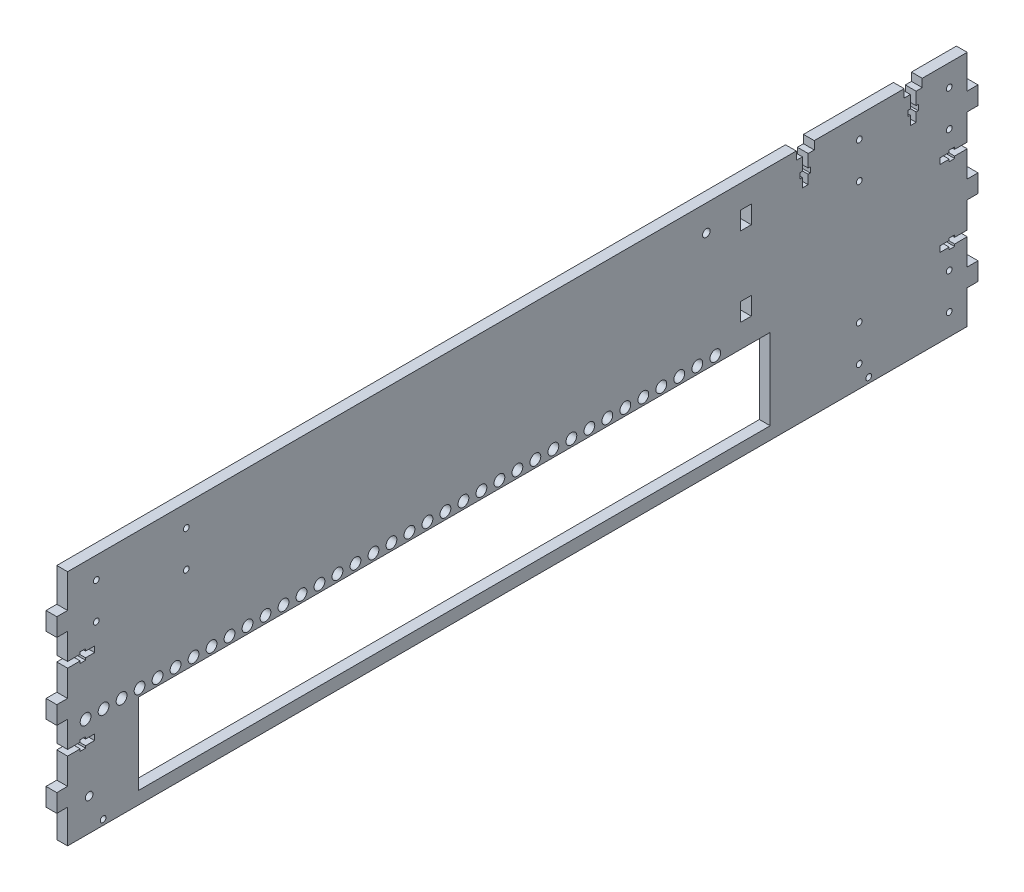
SolidWorks part; units mm, degrees
ref_plane "Front Plane" through (0, 0, 0) normal (0, 0, 1) x (1, 0, 0)
ref_plane "Top Plane" through (0, 0, 0) normal (0, 1, 0) x (1, 0, 0)
ref_plane "Right Plane" through (0, 0, 0) normal (1, 0, 0) x (0, 0, -1)
sketch "Sketch1" plane through (0, 0, 0) normal (1, 0, 0) x (0, 0, -1)
  line L1 (-250, -66) -> (250, -66)
  line L2 (-250, -66) -> (-250, 66)
  line L3 (-250, 66) -> (250, 66)
  line L4 (250, -66) -> (250, 66)
  line L5 (-250, -66) -> (250, 66) construction
  line L6 (-250, 66) -> (250, -66) construction
  point P0 (0, 0)
  dimension "D1" = 132
  dimension "D2" = 500
extrude "Boss-Extrude1" add sketch "Sketch1" along normal blind 6
sketch "Sketch4" plane through (0, 0, 250) normal (0, 0, 1) x (1, 0, 0)
  line L0 (0, 66) -> (0, -66) construction
  line L1 (0, 47.3321) -> (6, 47.3321)
  line L2 (0, 47.3321) -> (0, 37.3321)
  line L3 (0, 37.3321) -> (6, 37.3321)
  line L4 (6, 47.3321) -> (6, 37.3321)
  line L5 (6, 66) -> (6, -66) construction
  line L6 (0, 37.3321) -> (6, 37.3321) construction
  line L7 (0, -66) -> (0, 66) construction
  line L8 (6, 47.3321) -> (0, 47.3321) construction
  line L9 (0, -5) -> (6, -5) construction
  line L10 (0, -5) -> (6, -5)
  line L11 (0, -5) -> (0, 5)
  line L12 (0, 5) -> (6, 5)
  line L13 (6, -5) -> (6, 5)
  line L14 (6, -66) -> (6, 66) construction
  line L15 (6, 5) -> (0, 5) construction
  line L16 (6, -37.3321) -> (0, -37.3321) construction
  line L17 (0, -47.3321) -> (6, -47.3321)
  line L18 (0, -47.3321) -> (0, -37.3321)
  line L19 (0, -37.3321) -> (6, -37.3321)
  line L20 (6, -47.3321) -> (6, -37.3321)
  line L21 (0, -47.3321) -> (6, -47.3321) construction
extrude "Boss-Extrude2" add sketch "Sketch4" along normal blind 6
sketch "Sketch5" plane through (0, 0, 0) normal (-1, 0, 0) x (0, 0, 1)
  line L1 (250, 22.7661) -> (250, 19.5661) construction
  line L3 (250, 22.7661) -> (250, 19.5661) construction
  line L4 (250, -19.5661) -> (250, -22.7661) construction
  line L5 (250, -19.5661) -> (250, -22.7661) construction
  line L6 (250, 21.1661) -> (235, 21.1661) construction
  line L7 (250, -21.1661) -> (235, -21.1661) construction
  line L8 (250, -19.5661) -> (243, -19.5661)
  line L9 (250, 22.7661) -> (243, 22.7661)
  line L10 (250, -22.7661) -> (243, -22.7661)
  line L11 (250, 19.5661) -> (243, 19.5661)
  line L12 (250, -19.5661) -> (250, -22.7661)
  line L13 (235, -19.5661) -> (235, -22.7661)
  line L14 (250, 22.7661) -> (250, 19.5661)
  line L15 (235, 22.7661) -> (235, 19.5661)
  line L16 (240, 19.5661) -> (235, 19.5661)
  line L17 (243, 18.3661) -> (240, 18.3661)
  line L18 (243, 18.3661) -> (243, 19.5661)
  line L19 (243, 23.9661) -> (240, 23.9661)
  line L20 (240, 18.3661) -> (240, 19.5661)
  line L21 (243, 18.3661) -> (240, 23.9661) construction
  line L22 (243, 23.9661) -> (240, 18.3661) construction
  line L23 (243, -23.9661) -> (240, -23.9661)
  line L24 (243, -23.9661) -> (243, -22.7661)
  line L25 (243, -18.3661) -> (240, -18.3661)
  line L26 (240, -23.9661) -> (240, -22.7661)
  line L27 (243, -23.9661) -> (240, -18.3661) construction
  line L28 (243, -18.3661) -> (240, -23.9661) construction
  line L29 (250, 19.5661) -> (235, 19.5661) construction
  line L30 (243, 22.7661) -> (243, 23.9661)
  line L31 (240, 22.7661) -> (235, 22.7661)
  line L32 (250, 22.7661) -> (235, 22.7661) construction
  line L33 (240, 22.7661) -> (240, 23.9661)
  line L34 (240, -19.5661) -> (235, -19.5661)
  line L35 (250, -19.5661) -> (235, -19.5661) construction
  line L36 (240, -19.5661) -> (240, -18.3661)
  line L37 (240, -22.7661) -> (235, -22.7661)
  line L38 (250, -22.7661) -> (235, -22.7661) construction
  line L39 (243, -19.5661) -> (243, -18.3661)
  point P20 (241.5, 21.1661)
  point P25 (241.5, -21.1661)
  line M35 (250, -37.3321) -> (250, -5)
  line M39 (250, 5) -> (250, 37.3321)
  dimension "D3" = 1.6
  dimension "D4" = 7
  dimension "D5" = 3
  dimension "D6" = 5.6
  dimension "D1" = 15
  dimension "D7" = 7
  dimension "D8" = 3
  dimension "D9" = 5.6
  dimension "D2" = 1.6
extrude "Cut-Extrude3" cut sketch "Sketch5" against normal up to next contours L12 | L8 L39 L25 L36 L34 L13 L37 L26 L23 L24 L10 M35 | L33 L31 L15 L16 L20 L17 L18 L11 L9 L30 L19 M39 region at (0, -21.1661, 242.3696) region at (0, 21.1661, 242.3696)
sketch "Sketch6" plane through (0, 0, -250) normal (0, 0, -1) x (-1, 0, 0)
  line L0 (0, 47.3321) -> (0, 37.3321) construction
  line L1 (0, 37.3321) -> (-6, 37.3321) construction
  line L2 (-6, 37.3321) -> (-6, 47.3321) construction
  line L3 (-6, 47.3321) -> (0, 47.3321) construction
  line L4 (0, 5) -> (0, -5) construction
  line L5 (0, -5) -> (-6, -5) construction
  line L6 (-6, -5) -> (-6, 5) construction
  line L7 (-6, 5) -> (0, 5) construction
  line L8 (0, -37.3321) -> (0, -47.3321) construction
  line L9 (0, -47.3321) -> (-6, -47.3321) construction
  line L10 (-6, -47.3321) -> (-6, -37.3321) construction
  line L11 (-6, -37.3321) -> (0, -37.3321) construction
  line L12 (0, 47.3321) -> (0, 37.3321)
  line L13 (0, 37.3321) -> (-6, 37.3321)
  line L14 (-6, 37.3321) -> (-6, 47.3321)
  line L15 (-6, 47.3321) -> (0, 47.3321)
  line L16 (0, 5) -> (0, -5)
  line L17 (0, -5) -> (-6, -5)
  line L18 (-6, -5) -> (-6, 5)
  line L19 (-6, 5) -> (0, 5)
  line L20 (0, -37.3321) -> (0, -47.3321)
  line L21 (0, -47.3321) -> (-6, -47.3321)
  line L22 (-6, -47.3321) -> (-6, -37.3321)
  line L23 (-6, -37.3321) -> (0, -37.3321)
extrude "Boss-Extrude3" add sketch "Sketch6" along normal blind 6
sketch "Sketch7" plane through (0, 0, 0) normal (-1, 0, 0) x (0, 0, 1)
  line L0 (243, 19.5661) -> (250, 19.5661) construction
  line L2 (243, 19.5661) -> (243, 18.3661) construction
  line L3 (240, 18.3661) -> (243, 18.3661) construction
  line L4 (240, 19.5661) -> (240, 18.3661) construction
  line L5 (235, 19.5661) -> (240, 19.5661) construction
  line L6 (235, 19.5661) -> (235, 22.7661) construction
  line L7 (235, 22.7661) -> (240, 22.7661) construction
  line L8 (240, 23.9661) -> (240, 22.7661) construction
  line L9 (240, 23.9661) -> (243, 23.9661) construction
  line L10 (243, 23.9661) -> (243, 22.7661) construction
  line L11 (243, 22.7661) -> (250, 22.7661) construction
  line L12 (243, 19.5661) -> (250, 19.5661) construction
  line L13 (243, 19.5661) -> (243, 18.3661) construction
  line L14 (240, 18.3661) -> (243, 18.3661) construction
  line L15 (240, 19.5661) -> (240, 18.3661) construction
  line L16 (235, 19.5661) -> (240, 19.5661) construction
  line L17 (235, 19.5661) -> (235, 22.7661) construction
  line L18 (235, 22.7661) -> (240, 22.7661) construction
  line L19 (240, 23.9661) -> (240, 22.7661) construction
  line L20 (240, 23.9661) -> (243, 23.9661) construction
  line L21 (243, 23.9661) -> (243, 22.7661) construction
  line L22 (243, 22.7661) -> (250, 22.7661) construction
  line L23 (235, -22.7661) -> (240, -22.7661) construction
  line L24 (240, -22.7661) -> (240, -23.9661) construction
  line L25 (240, -23.9661) -> (243, -23.9661) construction
  line L26 (243, -22.7661) -> (243, -23.9661) construction
  line L27 (243, -22.7661) -> (250, -22.7661) construction
  line L28 (243, -19.5661) -> (250, -19.5661) construction
  line L29 (243, -18.3661) -> (243, -19.5661) construction
  line L30 (240, -18.3661) -> (243, -18.3661) construction
  line L31 (240, -18.3661) -> (240, -19.5661) construction
  line L32 (235, -19.5661) -> (240, -19.5661) construction
  line L33 (235, -22.7661) -> (235, -19.5661) construction
  line L34 (235, -22.7661) -> (240, -22.7661) construction
  line L35 (240, -22.7661) -> (240, -23.9661) construction
  line L36 (240, -23.9661) -> (243, -23.9661) construction
  line L37 (243, -22.7661) -> (243, -23.9661) construction
  line L38 (243, -22.7661) -> (250, -22.7661) construction
  line L39 (243, -19.5661) -> (250, -19.5661) construction
  line L40 (243, -18.3661) -> (243, -19.5661) construction
  line L41 (240, -18.3661) -> (243, -18.3661) construction
  line L42 (240, -18.3661) -> (240, -19.5661) construction
  line L43 (235, -19.5661) -> (240, -19.5661) construction
  line L44 (235, -22.7661) -> (235, -19.5661) construction
  line L45 (0, 0) -> (0, 57.5645) construction
  line L46 (-235, -22.7661) -> (-235, -19.5661)
  line L47 (-235, -19.5661) -> (-240, -19.5661)
  line L48 (-240, -18.3661) -> (-240, -19.5661)
  line L49 (-240, -18.3661) -> (-243, -18.3661)
  line L50 (-243, -18.3661) -> (-243, -19.5661)
  line L51 (-243, -19.5661) -> (-250, -19.5661)
  line L52 (-243, -22.7661) -> (-250, -22.7661)
  line L53 (-243, -22.7661) -> (-243, -23.9661)
  line L54 (-240, -23.9661) -> (-243, -23.9661)
  line L55 (-240, -22.7661) -> (-240, -23.9661)
  line L56 (-235, -22.7661) -> (-240, -22.7661)
  line L57 (-243, 22.7661) -> (-250, 22.7661)
  line L58 (-243, 23.9661) -> (-243, 22.7661)
  line L59 (-240, 23.9661) -> (-243, 23.9661)
  line L60 (-240, 23.9661) -> (-240, 22.7661)
  line L61 (-235, 22.7661) -> (-240, 22.7661)
  line L62 (-235, 19.5661) -> (-235, 22.7661)
  line L63 (-235, 19.5661) -> (-240, 19.5661)
  line L64 (-240, 19.5661) -> (-240, 18.3661)
  line L65 (-240, 18.3661) -> (-243, 18.3661)
  line L66 (-243, 19.5661) -> (-243, 18.3661)
  line L67 (-243, 19.5661) -> (-250, 19.5661)
  line L68 (-250, 22.7661) -> (-250, 19.5661)
  line L69 (-250, -19.5661) -> (-250, -22.7661)
extrude "Cut-Extrude4" cut sketch "Sketch7" against normal up to next
sketch "Sketch8" plane through (0, 0, 0) normal (-1, 0, 0) x (0, 0, 1)
  line L0 (210, -14.55) -> (-140, -14.55) construction
  line L1 (210, -14.55) -> (-140, -14.55) construction
  line L2 (210, -14.55) -> (210, -59) construction
  line L3 (210, -14.55) -> (210, -59) construction
  line L186 (-140, -14.55) -> (-140, -59) construction
  line L187 (-140, -59) -> (210, -59) construction
  line L188 (210.5, -14.05) -> (210.5, -59)
  line L189 (210.5, -14.05) -> (-140.5, -14.05)
  line L190 (-140.5, -14.05) -> (-140.5, -59)
  line L191 (-140.5, -59) -> (210.5, -59)
  dimension "D1" = 0.5
extrude "Cut-Extrude5" cut sketch "Sketch8" against normal up to next
sketch "Sketch11" plane through (6, 0, 0) normal (1, 0, 0) x (0, 0, -1)
  line L0 (130, 43) -> (130, 53) construction
  line L1 (130, 53) -> (124, 53) construction
  line L2 (124, 53) -> (124, 43) construction
  line L3 (124, 43) -> (130, 43) construction
  line L4 (130, -1) -> (130, 9) construction
  line L5 (130, 9) -> (124, 9) construction
  line L6 (124, 9) -> (124, -1) construction
  line L7 (124, -1) -> (130, -1) construction
  line L8 (130, 43) -> (130, 53)
  line L9 (130, 53) -> (124, 53)
  line L10 (124, 53) -> (124, 43)
  line L11 (124, 43) -> (130, 43)
  line L12 (130, -1) -> (130, 9)
  line L13 (130, 9) -> (124, 9)
  line L14 (124, 9) -> (124, -1)
  line L15 (124, -1) -> (130, -1)
extrude "Cut-Extrude8" cut sketch "Sketch11" against normal up to next
sketch "Sketch12" plane through (0, 0, 0) normal (-1, 0, 0) x (0, 0, 1)
  line L0 (-124, 53) -> (-124, 43) construction
  line L1 (-250, 66) -> (250, 66) construction
  circle A0 centre (-105, 51.5) radius 2.1
  dimension "D1" = 19
  dimension "D3" = 4.2
  dimension "D2" = 14.5
extrude "Cut-Extrude9" cut sketch "Sketch12" against normal up to next
sketch "Sketch13" plane through (0, 66, 0) normal (0, 1, 0) x (1, 0, 0)
  line L0 (6, 250) -> (6, -250) construction
  line L1 (0, 215) -> (6, 215)
  line L2 (0, 215) -> (0, 225)
  line L3 (0, 225) -> (6, 225)
  line L4 (6, 215) -> (6, 225)
  line L5 (0, 215) -> (6, 225) construction
  line L6 (0, 225) -> (6, 215) construction
  line L7 (6, 225) -> (0, 225) construction
  line L8 (6, 165) -> (0, 165) construction
  line L9 (0, 155) -> (6, 155)
  line L10 (0, 155) -> (0, 165)
  line L11 (0, 165) -> (6, 165)
  line L12 (6, 155) -> (6, 165)
  line L13 (0, 155) -> (6, 165) construction
  line L14 (0, 165) -> (6, 155) construction
  point P0 (3, 220)
  point P10 (3, 160)
extrude "Cut-Extrude10" cut sketch "Sketch13" against normal blind 4.5
sketch "Sketch14" plane through (0, 0, 0) normal (-1, 0, 0) x (0, 0, 1)
  circle A0 centre (240, -10) radius 3 construction
  circle A1 centre (240, -10) radius 3
  circle A2 centre (230, -10) radius 3
  circle A3 centre (220, -10) radius 3
  circle A4 centre (210, -10) radius 3
  circle A5 centre (200, -10) radius 3
  circle A6 centre (190, -10) radius 3
  circle A7 centre (180, -10) radius 3
  circle A8 centre (170, -10) radius 3
  circle A9 centre (160, -10) radius 3
  circle A10 centre (150, -10) radius 3
  circle A11 centre (140, -10) radius 3
  circle A12 centre (130, -10) radius 3
  circle A13 centre (120, -10) radius 3
  circle A14 centre (110, -10) radius 3
  circle A15 centre (100, -10) radius 3
  circle A16 centre (90, -10) radius 3
  circle A17 centre (80, -10) radius 3
  circle A18 centre (70, -10) radius 3
  circle A19 centre (60, -10) radius 3
  circle A20 centre (50, -10) radius 3
  circle A21 centre (40, -10) radius 3
  circle A22 centre (30, -10) radius 3
  circle A23 centre (20, -10) radius 3
  circle A24 centre (10, -10) radius 3
  circle A25 centre (0, -10) radius 3
  circle A26 centre (-10, -10) radius 3
  circle A27 centre (-20, -10) radius 3
  circle A28 centre (-30, -10) radius 3
  circle A29 centre (-40, -10) radius 3
  circle A30 centre (-50, -10) radius 3
  circle A31 centre (-60, -10) radius 3
  circle A32 centre (-70, -10) radius 3
  circle A33 centre (-80, -10) radius 3
  circle A34 centre (-90, -10) radius 3
  circle A35 centre (-100, -10) radius 3
  circle A36 centre (-110, -10) radius 3
  dimension "D1" = 36
extrude "Cut-Extrude11" cut sketch "Sketch14" against normal up to next (6 mm away)
sketch "Sketch15" plane through (6, 0, 0) normal (1, 0, 0) x (0, 0, -1)
  line L0 (160, 61.5) -> (160, 46.5) construction
  line L1 (155, 61.5) -> (165, 61.5) construction
  line L2 (220, 61.5) -> (220, 46.5) construction
  line L3 (215, 61.5) -> (225, 61.5) construction
  line L4 (160, 46.5) -> (220, 46.5) construction
  line L5 (190, 46.5) -> (190, 66) construction
  line L6 (215, 66) -> (165, 66) construction
  line L7 (158.4, 61.5) -> (158.4, 54.5)
  line L8 (161.6, 61.5) -> (161.6, 54.5)
  line L9 (158.4, 61.5) -> (161.6, 61.5)
  line L10 (158.4, 46.5) -> (161.6, 46.5)
  line L11 (161.6, 51.5) -> (162.8, 51.5)
  line L12 (157.2, 54.5) -> (158.4, 54.5)
  line L13 (157.2, 54.5) -> (157.2, 51.5)
  line L14 (157.2, 51.5) -> (158.4, 51.5)
  line L15 (162.8, 54.5) -> (162.8, 51.5)
  line L16 (157.2, 54.5) -> (162.8, 51.5) construction
  line L17 (157.2, 51.5) -> (162.8, 54.5) construction
  line L18 (161.6, 54.5) -> (162.8, 54.5)
  line L19 (158.4, 51.5) -> (158.4, 46.5)
  line L20 (158.4, 61.5) -> (158.4, 46.5) construction
  line L21 (161.6, 51.5) -> (161.6, 46.5)
  line L22 (161.6, 61.5) -> (161.6, 46.5) construction
  line L23 (222.8, 51.5) -> (217.2, 54.5) construction
  line L24 (222.8, 54.5) -> (217.2, 51.5) construction
  line L25 (220, 61.5) -> (220, 46.5) construction
  line L26 (218.4, 51.5) -> (218.4, 46.5)
  line L27 (221.6, 51.5) -> (221.6, 46.5)
  line L28 (218.4, 54.5) -> (217.2, 54.5)
  line L29 (217.2, 54.5) -> (217.2, 51.5)
  line L30 (222.8, 51.5) -> (221.6, 51.5)
  line L31 (222.8, 54.5) -> (222.8, 51.5)
  line L32 (222.8, 54.5) -> (221.6, 54.5)
  line L33 (218.4, 51.5) -> (217.2, 51.5)
  line L34 (221.6, 46.5) -> (218.4, 46.5)
  line L35 (221.6, 61.5) -> (218.4, 61.5)
  line L36 (218.4, 61.5) -> (218.4, 54.5)
  line L37 (221.6, 61.5) -> (221.6, 54.5)
  point P16 (160, 53)
  point P37 (220, 53)
  dimension "D3" = 15
  dimension "D4" = 7
  dimension "D5" = 3
  dimension "D6" = 5.6
  dimension "D1" = 1.6
  dimension "D2" = 1.6
extrude "Cut-Extrude12" cut sketch "Sketch15" against normal up to next
sketch "Sketch17" plane through (6, 0, 0) normal (1, 0, 0) x (0, 0, -1)
  circle A0 centre (-238, -48) radius 2.1 construction
  circle A1 centre (-238, -48) radius 2.1
extrude "Cut-Extrude14" cut sketch "Sketch17" against normal through all
sketch "Sketch18" plane through (6, 0, 0) normal (1, 0, 0) x (0, 0, -1)
  line L0 (-210.5, -59) -> (-250, -59) construction
  line L1 (-250, -47.3321) -> (-250, -66) construction
  line L2 (-230.25, -59) -> (-230.25, -66) construction
  line L3 (-250, -66) -> (250, -66) construction
  line L4 (140.5, -59) -> (250, -59) construction
  line L5 (250, -66) -> (250, -47.3321) construction
  line L6 (195.25, -59) -> (195.25, -66) construction
  circle A0 centre (-230.25, -63) radius 1.6
  circle A1 centre (195.25, -63) radius 1.6
  dimension "D1" = 3.2
  dimension "D2" = 3
extrude "Cut-Extrude15" cut sketch "Sketch18" against normal through all
sketch "Sketch19" plane through (6, 0, 0) normal (1, 0, 0) x (0, 0, -1)
  circle A1 centre (240, -34) radius 1.6
  circle A2 centre (240, -34) radius 1.6
  circle A3 centre (240, 54) radius 1.6
  circle A5 centre (240, 54) radius 1.6
  circle A7 centre (240, -54) radius 1.6
  circle A8 centre (240, -54) radius 1.6
  circle A11 centre (190, -54) radius 1.6
  circle A12 centre (190, -54) radius 1.6
  circle A15 centre (190, -34) radius 1.6
  circle A16 centre (190, -34) radius 1.6
  circle A24 centre (190, 34) radius 1.6
  circle A25 centre (190, 34) radius 1.6
  circle A30 centre (190, 54) radius 1.6
  circle A31 centre (190, 54) radius 1.6
  circle A32 centre (240, 34) radius 1.6
  circle A33 centre (240, 34) radius 1.6
  circle A56 centre (-184, 34) radius 1.6 construction
  circle A57 centre (-234, 34) radius 1.6 construction
  circle A58 centre (-184, 54) radius 1.6 construction
  circle A59 centre (-234, 54) radius 1.6 construction
  circle A60 centre (-184, 34) radius 1.6
  circle A61 centre (-234, 34) radius 1.6
  circle A62 centre (-184, 54) radius 1.6
  circle A63 centre (-234, 54) radius 1.6
  dimension "D1" = 0
  dimension "D2" = 0
  dimension "D5" = 0
  dimension "D7" = 0
  dimension "D9" = 0
  dimension "D12" = 0
  dimension "D15" = 0
  dimension "D16" = 0
extrude "Cut-Extrude16" cut sketch "Sketch19" against normal through all
